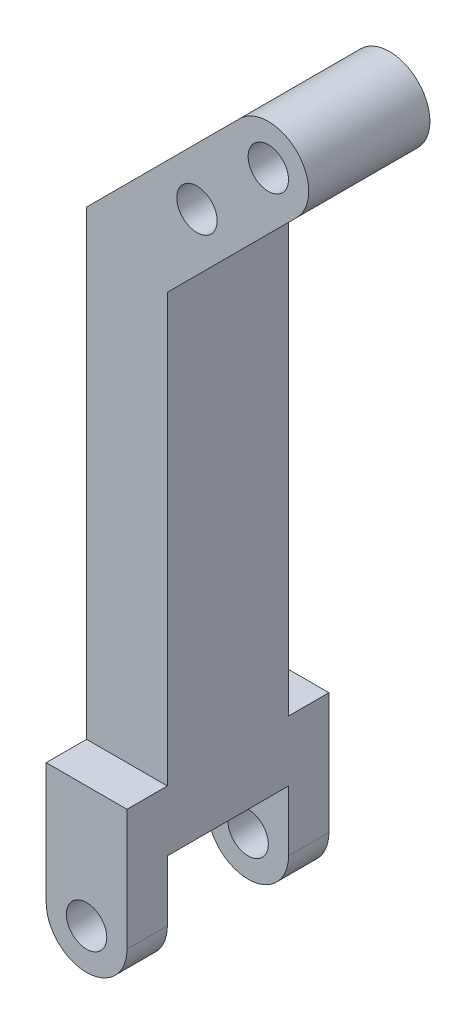
SolidWorks part; units mm, degrees
ref_plane "前视基准面" through (0, 0, 0) normal (0, 0, 1) x (1, 0, 0)
ref_plane "上视基准面" through (0, 0, 0) normal (0, 1, 0) x (1, 0, 0)
ref_plane "右视基准面" through (0, 0, 0) normal (1, 0, 0) x (0, 0, -1)
other "Configuration Table"
sketch "草图1" plane through (0, 0, 0) normal (0, 0, 1) x (1, 0, 0)
  circle A0 centre (0, 0) radius 20
  circle A1 centre (0, 0) radius 10
  dimension "D1" = 40
  dimension "D2" = 20
extrude "凸台-拉伸1" add sketch "草图1" along normal blind 60 contours A1 | A0 region at (0, 0, 0)
ref_plane "基准面1" through (0, 0, 30) normal (0, 0, 1) x (1, 0, 0)
sketch "草图2" plane through (0, 0, 30) normal (0, 0, 1) x (1, 0, 0)
  line L0 (0, 0) -> (-70, -70) construction
  line L1 (-70, -70) -> (-70, -320) construction
  line L2 (0, -57.3148) -> (0, 49.9409) construction
  line L3 (-56.8582, 0) -> (46.4003, 0) construction
  line L4 (-14.1421, 14.1421) -> (-90, -61.7157)
  line L5 (14.1421, -14.1421) -> (-50, -78.2843)
  line L6 (-90, -61.7157) -> (-90, -320)
  line L7 (-50, -78.2843) -> (-50, -320)
  line L8 (-90, -320) -> (-50, -320)
  circle A2 centre (0, 0) radius 20 construction
  arc A3 (-14.1421, 14.1421) -> (14.1421, -14.1421) centre (0, 0) ccw
  dimension "D1" = 45
  dimension "D2" = 250
  dimension "D3" = 70
  dimension "D4" = 40
  dimension "D5" = 40
extrude "凸台-拉伸2" add sketch "草图2" along normal mid plane 60 contours L7 L8 L6 L4 A3 L5
sketch "草图4" plane through (0, 0, 60) normal (0, 0, 1) x (1, 0, 0)
  line L0 (-90, -61.7157) -> (-90, -320) construction
  line L1 (-90, -290) -> (-50, -290)
  line L2 (-90, -290) -> (-90, -350)
  line L4 (-50, -290) -> (-50, -350)
  line L5 (-50, -78.2843) -> (-50, -320) construction
  line L6 (-90, -320) -> (-50, -320) construction
  arc A0 (-90, -350) -> (-50, -350) centre (-70, -350) ccw
  circle A1 centre (-70, -350) radius 10
  dimension "D3" = 20
  dimension "D1" = 30
  dimension "D2" = 30
extrude "凸台-拉伸3" add sketch "草图4" along normal blind 20
mirror "镜向1" about plane through (0, 0, 30) normal (0, 0, 1) of "凸台-拉伸3"
sketch "草图5" plane through (0, 0, 0) normal (0, 1, 0) x (1, 0, 0)
  line L0 (0, 0) -> (0, -78.0582) construction
ref_plane "基准面2" through (-70, 0, 0) normal (-1, 0, 0) x (0, 0, 1)
sketch "草图7" plane through (-70, 0, 0) normal (-1, 0, 0) x (0, 0, 1)
  line L0 (-34.1239, -350) -> (109.535, -350) construction
sketch "草图8" plane through (0, 0, 60) normal (0, 0, 1) x (1, 0, 0)
  line L0 (0, 0) -> (-70, -70) construction
  circle A0 centre (-35.3553, -35.3553) radius 10
  dimension "D1" = 20
  dimension "D2" = 50
extrude "切除-拉伸1" cut sketch "草图8" against normal blind 100
